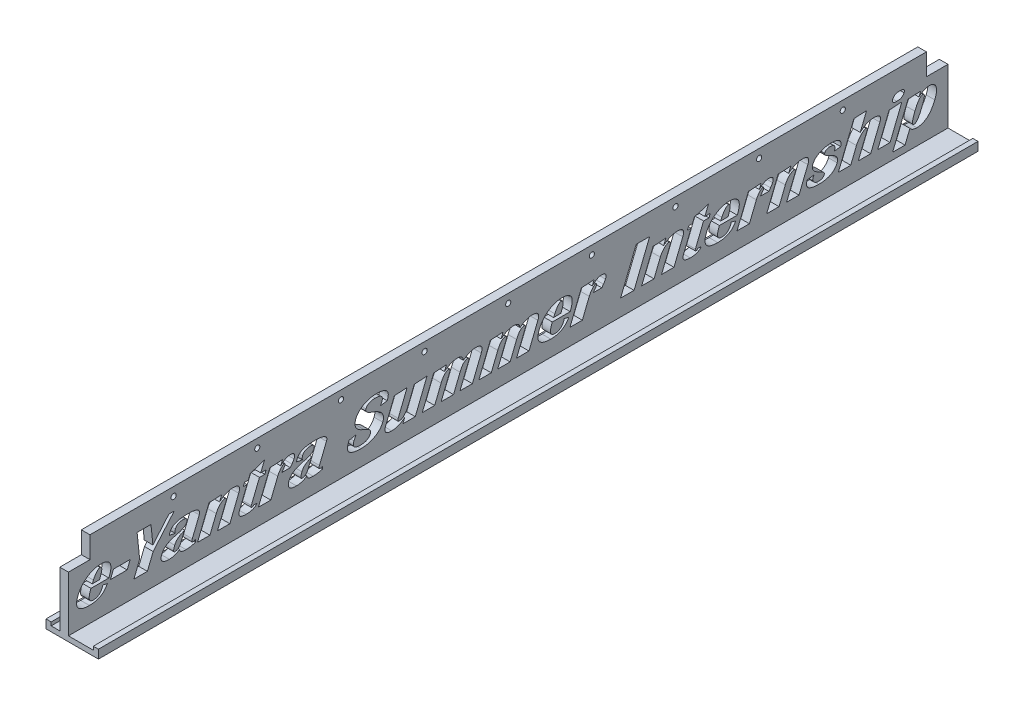
SolidWorks part; units mm, degrees
material "Acrylic (Medium-high impact)"
ref_plane "Front Plane" through (0, 0, 0) normal (0, 0, 1) x (1, 0, 0)
ref_plane "Top Plane" through (0, 0, 0) normal (0, 1, 0) x (1, 0, 0)
ref_plane "Right Plane" through (0, 0, 0) normal (1, 0, 0) x (0, 0, -1)
sketch "Sketch1" plane through (0, 0, 0) normal (0, 0, 1) x (1, 0, 0)
  line L0 (0, 10) -> (0, 0)
  line L1 (0, 0) -> (60.8, 0)
  line L2 (60.8, 0) -> (60.8, 10)
  line L3 (60.8, 10) -> (54.8, 10)
  line L4 (54.8, 10) -> (54.8, 6)
  line L5 (54.8, 6) -> (26, 6)
  line L6 (26, 6) -> (26, 95)
  line L7 (26, 95) -> (16, 95)
  line L8 (16, 95) -> (16, 6)
  line L9 (16, 6) -> (6, 6)
  line L10 (6, 6) -> (6, 10)
  line L11 (6, 10) -> (0, 10)
  dimension "D1" = 10
  dimension "D2" = 10
  dimension "D3" = 6
  dimension "D4" = 6
  dimension "D6" = 10
  dimension "D7" = 60.8
  dimension "D8" = 95
extrude "Boss-Extrude1" add sketch "Sketch1" along normal blind 1020
sketch "Sketch2" plane through (26, 0, 0) normal (1, 0, 0) x (0, 0, -1)
  line L0 (-1052.1126, 85) -> (45.5589, 85) construction
  line L1 (-1020, 95) -> (-995, 95)
  line L2 (-1020, 95) -> (-1020, 70)
  line L3 (-1020, 70) -> (-995, 70)
  line L4 (-995, 95) -> (-995, 70)
  line L5 (0, 95) -> (-25, 95)
  line L6 (0, 95) -> (0, 70)
  line L7 (0, 70) -> (-25, 70)
  line L8 (-25, 95) -> (-25, 70)
  line L9 (-1020, 95) -> (0, 95) construction
  dimension "D1" = 25
  dimension "D2" = 25
  dimension "D3" = 25
  dimension "D4" = 25
  dimension "D5" = 10
extrude "Cut-Extrude1" cut sketch "Sketch2" against normal blind 10
sketch "Sketch3" plane through (26, 0, 0) normal (1, 0, 0) x (0, 0, -1)
  line L0 (-995, 70) -> (-995, 95) construction
  line L1 (-995, 95) -> (-25, 95) construction
  circle A0 centre (-898, 85) radius 3
  dimension "D3" = 6
  dimension "D1" = 97
  dimension "D2" = 10
extrude "Cut-Extrude2" cut sketch "Sketch3" against normal blind 10
pattern_linear "LPattern1" count 9 spacing 97 along (0, 0, -1) of "Cut-Extrude2"
sketch "Sketch4" plane through (26, 0, 0) normal (1, 0, 0) x (0, 0, -1)
  text T0 "e-Yantra Summer Internship    Programme 2018 " font "Britannic Bold" height 45
extrude "Cut-Extrude3" cut sketch "Sketch4" against normal blind 10
